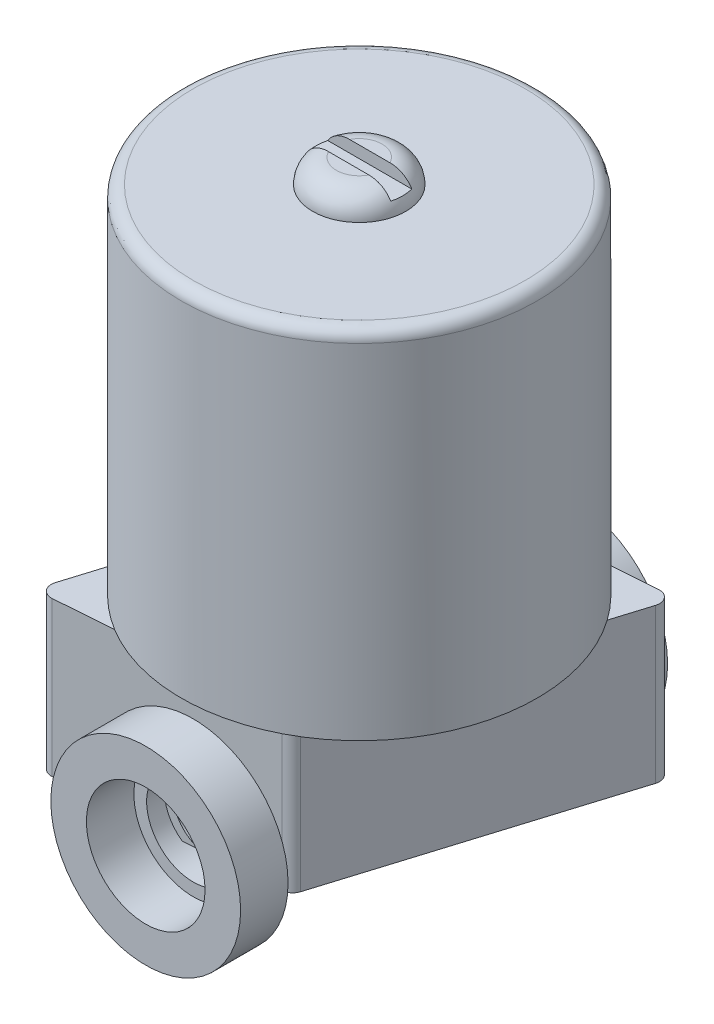
SolidWorks part; units mm, degrees
ref_plane "Front Plane" through (0, 0, 0) normal (0, 0, 1) x (1, 0, 0)
ref_plane "Top Plane" through (0, 0, 0) normal (0, 1, 0) x (1, 0, 0)
ref_plane "Right Plane" through (0, 0, 0) normal (1, 0, 0) x (0, 0, -1)
sketch "Sketch1" plane through (0, 0, 0) normal (0, 1, 0) x (1, 0, 0)
  line L0 (0, 35.0235) -> (0, -39.3926) construction
  line L1 (-61.296, 0) -> (56.9698, 0) construction
  circle A0 centre (0, 0) radius 15
  dimension "D1" = 30
extrude "Boss-Extrude1" add sketch "Sketch1" along normal blind 30
sketch "Sketch2" plane through (0, 0, 0) normal (0, -1, 0) x (1, 0, 0)
  line L0 (0, 22.4102) -> (0, -26.943) construction
  line L1 (-30.3165, 0) -> (30.7581, 0) construction
  line L2 (-5.1275, -9.3104) -> (11.2477, -10.5474) construction
  line L3 (24.3926, -24.3926) -> (-24.3926, 24.3926) construction
  line L4 (23.6068, 23.6068) -> (-23.6068, -23.6068) construction
  line L5 (11.2477, -10.5474) -> (5.1275, 9.3104) construction
  line L6 (5.1275, 9.3104) -> (-11.2477, 10.5474) construction
  line L7 (-11.2477, 10.5474) -> (-5.1275, -9.3104) construction
  line L8 (6.9998, 16.8991) -> (-6.9998, -16.8991) construction
  line L9 (-12.7184, 13.1656) -> (5.2827, 11.8058)
  line L10 (-13.7494, 11.8739) -> (-6.701, -10.9952)
  line L11 (6.163, 11.1031) -> (13.2113, -11.766)
  line L12 (-5.8207, -11.6979) -> (12.1804, -13.0577)
  arc A0 (-13.7494, 11.8739) -> (-12.7184, 13.1656) centre (-12.7937, 12.1685) cw
  circle A1 centre (-7.7782, 7.7782) radius 2.5
  circle A2 centre (7.7782, -7.7782) radius 2.5
  circle A3 centre (0, 0) radius 15 construction
  arc A4 (12.1804, -13.0577) -> (13.2113, -11.766) centre (12.2557, -12.0605) ccw
  arc A5 (-6.701, -10.9952) -> (-5.8207, -11.6979) centre (-5.7454, -10.7007) ccw
  arc A6 (6.163, 11.1031) -> (5.2827, 11.8058) centre (5.2074, 10.8086) ccw
  dimension "D1" = 5
  dimension "D2" = 5
  dimension "D7" = 1
  dimension "D8" = 1
  dimension "D6" = 22.5
  dimension "D10" = 1
  dimension "D3" = 11
  dimension "D4" = 11
  dimension "D5" = 45
  dimension "D9" = 45
  dimension "D12" = 2.5
  dimension "D13" = 2
extrude "Boss-Extrude2" add sketch "Sketch2" along normal blind 13
ref_plane "Plane1" through (0, 0, 14) normal (0, 0, 1) x (1, 0, 0)
sketch "Sketch3" plane through (0, 0, 14) normal (0, 0, 1) x (1, 0, 0)
  line L0 (5.2827, 0) -> (-7.8269, 0) construction
  circle A0 centre (0, -10) radius 5
  circle A1 centre (0, -10) radius 3.922
  dimension "D1" = 10
  dimension "D2" = 10
extrude "Boss-Extrude3" add sketch "Sketch3" against normal blind 28
sketch "Sketch4" plane through (0, 0, 14) normal (0, 0, 1) x (1, 0, 0)
  circle A0 centre (0, -10) radius 3.2134
  arc A1 (2.5263, -13) -> (-2.5263, -13) centre (0, -10) ccw construction
extrude "Cut-Extrude1" cut sketch "Sketch4" against normal through all
fillet "Fillet2" radius 1 1 edges at (0, 30, 15)
sketch "Sketch5" plane through (0, 0, -14) normal (0, 0, -1) x (-1, 0, 0)
  circle A0 centre (0, -10) radius 5
  circle A1 centre (0, -10) radius 8
  arc A2 (2.5263, -13) -> (-2.5263, -13) centre (0, -10) ccw construction
  dimension "D1" = 3
  dimension "D2" = 10
extrude "Boss-Extrude4" add sketch "Sketch5" along normal blind 4
sketch "Sketch6" plane through (0, 0, 14) normal (0, 0, 1) x (1, 0, 0)
  circle A0 centre (0, -10) radius 5
  circle A1 centre (0, -10) radius 8
  dimension "D1" = 10
  dimension "D2" = 3
extrude "Boss-Extrude6" add sketch "Sketch6" along normal blind 4 separate body
sketch "Sketch8" plane through (0, 30, 0) normal (0, 1, 0) x (1, 0, 0)
  line L0 (0, 21.2896) -> (0, -23.7442) construction
  line L1 (-20.3927, 0) -> (19.3542, 0) construction
  circle A0 centre (0, 0) radius 3.9226
extrude "Boss-Extrude7" add sketch "Sketch8" along normal blind 2
fillet "Fillet3" radius 2 1 edges at (0, 32, 3.9226)
sketch "Sketch9" plane through (0, 32, 0) normal (0, 1, 0) x (1, 0, 0)
  line L0 (-4.9686, 0) -> (4.3659, 0) construction
  line L2 (-4.5019, 0.8899) -> (4.3659, 0.8899)
  line L3 (-4.5019, 0.8899) -> (-4.5019, -0.8899)
  line L4 (-4.5019, -0.8899) -> (4.3659, -0.8899)
  line L5 (4.3659, 0.8899) -> (4.3659, -0.8899)
extrude "Cut-Extrude3" cut sketch "Sketch9" against normal blind 1
